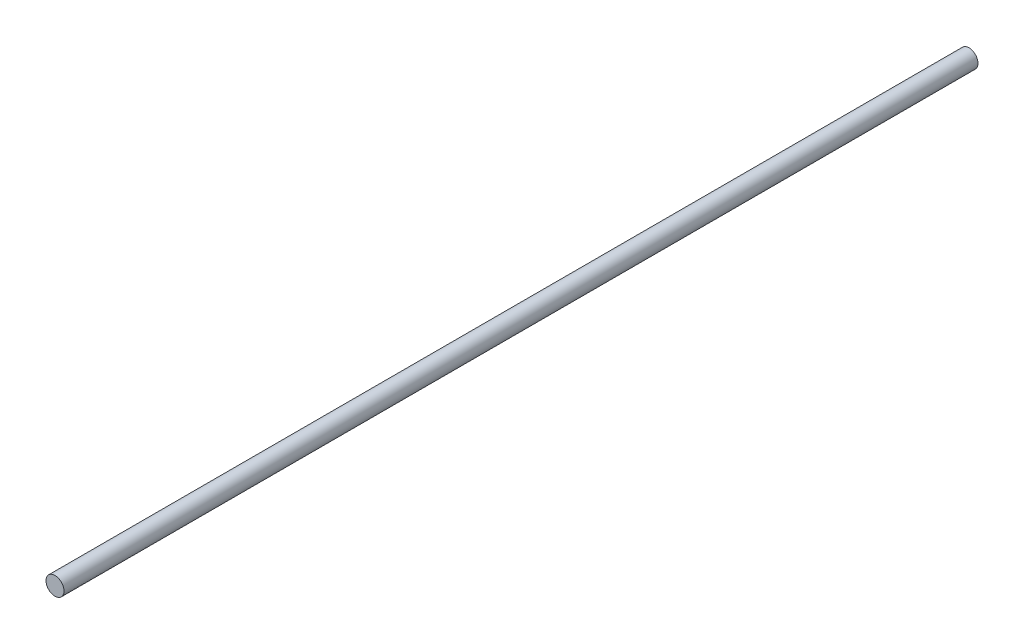
SolidWorks part; units mm, degrees
material "AISI 316 Stainless Steel Sheet (SS)"
ref_plane "Front (1)" through (0, 0, 0) normal (0, 0, 1) x (1, 0, 0)
ref_plane "Top (2)" through (0, 0, 0) normal (0, 1, 0) x (1, 0, 0)
ref_plane "Right (3)" through (0, 0, 0) normal (1, 0, 0) x (0, 0, -1)
ref_axis "X Axis" through (13.5064, 0, 0) along (-1, 0, 0)
ref_axis "Y Axis" through (0, 12.3593, 0) along (0, -1, 0)
ref_axis "Z Axis" through (0, 0, 14.1119) along (0, 0, -1)
sketch "Sketch2" plane through (0, 0, 0) normal (1, 0, 0) x (0, 0, -1)
  line L0 (-72.9, 0) -> (0, 0) construction
  line L1 (-72.9, 0) -> (332.9, 0)
  line L2 (-72.9, 0) -> (-72.9, 4)
  line L3 (-72.9, 4) -> (332.9, 4)
  line L4 (332.9, 0) -> (332.9, 4)
  dimension "D1" = 8
  dimension "D2" = 405.8
  dimension "D3" = 11.3
  dimension "D4" = 11.3
revolve "Revolve1" add sketch "Sketch2" angle 360 about L0
cosmetic thread "Cosmetic Thread2" parameters "D2"=6.891
